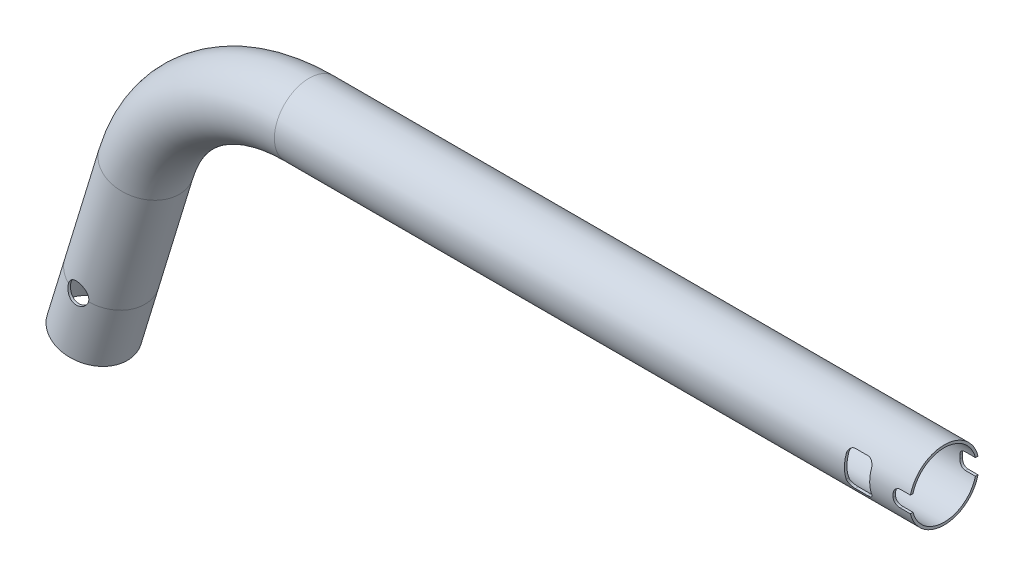
SolidWorks part; units mm, degrees
ref_plane "Front Plane" through (0, 0, 0) normal (0, 0, 1) x (1, 0, 0)
ref_plane "Top Plane" through (0, 0, 0) normal (0, 1, 0) x (1, 0, 0)
ref_plane "Right Plane" through (0, 0, 0) normal (1, 0, 0) x (0, 0, -1)
sketch "Sketch1" plane through (0, 0, 0) normal (0, 0, 1) x (1, 0, 0)
  line L0 (-92.2396, 0) -> (92.2396, 0)
  line L1 (-143.88, -38.2119) -> (-154.7604, -73.8)
  line L2 (92.2396, 0) -> (108.8396, 0)
  line L3 (-154.7604, -73.8) -> (-160.3247, -92)
  arc A0 (-92.2396, 0) -> (-143.88, -38.2119) centre (-92.2396, -54) ccw
  point P4 (0, 0)
  point P10 (-154.7604, -73.8)
  dimension "D2" = 54
  dimension "D1" = 73
  dimension "D3" = 73.8
  dimension "D4" = 247
  dimension "D5" = 92
  dimension "D6" = 73
  dimension "D7" = 16.6
ref_plane "Plane1" through (92.2396, 0, 0) normal (1, 0, 0) x (0, 0, -1)
sketch "Sketch3" plane through (92.2396, 0, 0) normal (1, 0, 0) x (0, 0, -1)
  circle A0 centre (0, 0) radius 11
  circle A1 centre (0, 0) radius 10.2
  dimension "D1" = 0.8
sweep "Sweep2" add profiles "Sketch3" path "Sketch1"
ref_axis "Axis1" through (108.8396, 0, 0) along (-1, 0, 0)
ref_axis "Axis2" through (-142.0816, -32.3296, 0) along (-0.2924, -0.9563, 0)
sketch "Sketch4" plane through (0, 0, 0) normal (0, 0, 1) x (1, 0, 0)
  line L0 (-165.2798, -70.5839) -> (-144.2411, -77.0161) construction
  line L1 (92.2396, -101.4635) -> (92.2396, 101.4635) construction
  line L2 (108.8396, 0) -> (92.2396, 0) construction
  line L3 (108.8396, -11) -> (108.8396, 11) construction
  line L4 (108.8396, 0) -> (-92.2396, 0) construction
  line L5 (108.8396, 2.5555) -> (108.8396, -2.5555)
  line L6 (90.2396, -5.5) -> (94.2396, -5.5)
  line L7 (88.2396, -3.5) -> (88.2396, 3.5)
  line L8 (90.2396, 5.5) -> (94.2396, 5.5)
  line L9 (96.2396, -3.5) -> (96.2396, 3.5)
  line L10 (88.2396, -5.5) -> (96.2396, 5.5) construction
  line L11 (88.2396, 5.5) -> (96.2396, -5.5) construction
  line L12 (105.6396, -2.5555) -> (108.8396, -2.5555)
  line L13 (103.6396, -0.5555) -> (103.6396, 0.5555)
  line L14 (105.6396, 2.5555) -> (108.8396, 2.5555)
  line L16 (103.6396, -2.5555) -> (108.8396, 0) construction
  line L17 (103.6396, 2.5555) -> (108.8396, 0) construction
  circle A0 centre (-154.7604, -73.8) radius 3.3
  arc A1 (90.2396, -5.5) -> (88.2396, -3.5) centre (90.2396, -3.5) cw
  arc A2 (96.2396, -3.5) -> (94.2396, -5.5) centre (94.2396, -3.5) cw
  arc A3 (94.2396, 5.5) -> (96.2396, 3.5) centre (94.2396, 3.5) cw
  arc A4 (90.2396, 5.5) -> (88.2396, 3.5) centre (90.2396, 3.5) ccw
  arc A5 (105.6396, -2.5555) -> (103.6396, -0.5555) centre (105.6396, -0.5555) cw
  arc A6 (103.6396, 0.5555) -> (105.6396, 2.5555) centre (105.6396, 0.5555) cw
  dimension "D1" = 16.6
  dimension "D4" = 2
  dimension "D5" = 2
  dimension "D2" = 8
  dimension "D3" = 11
extrude "Cut-Extrude1" cut sketch "Sketch4" along normal up to next
sketch "Sketch5" plane through (0, 0, 0) normal (0, 0, 1) x (1, 0, 0)
  line L0 (-164.5147, -70.8178) -> (-145.0061, -76.7822) construction
  circle A0 centre (-154.7604, -73.8) radius 3.3
extrude "Cut-Extrude2" cut sketch "Sketch5" against normal through all
sketch "Sketch6" plane through (0, 0, 0) normal (0, 0, 1) x (1, 0, 0)
  line L1 (108.8396, 2.5555) -> (105.6396, 2.5555)
  line L2 (108.8396, 2.5555) -> (108.8396, -2.5555)
  line L3 (108.8396, -2.5555) -> (105.6396, -2.5555)
  line L4 (103.6396, 0.5555) -> (103.6396, -0.5555)
  arc A0 (105.6396, -2.5555) -> (103.6396, -0.5555) centre (105.6396, -0.5555) cw
  arc A1 (103.6396, 0.5555) -> (105.6396, 2.5555) centre (105.6396, 0.5555) cw
  dimension "D1" = 2
extrude "Cut-Extrude3" cut sketch "Sketch6" against normal through all
